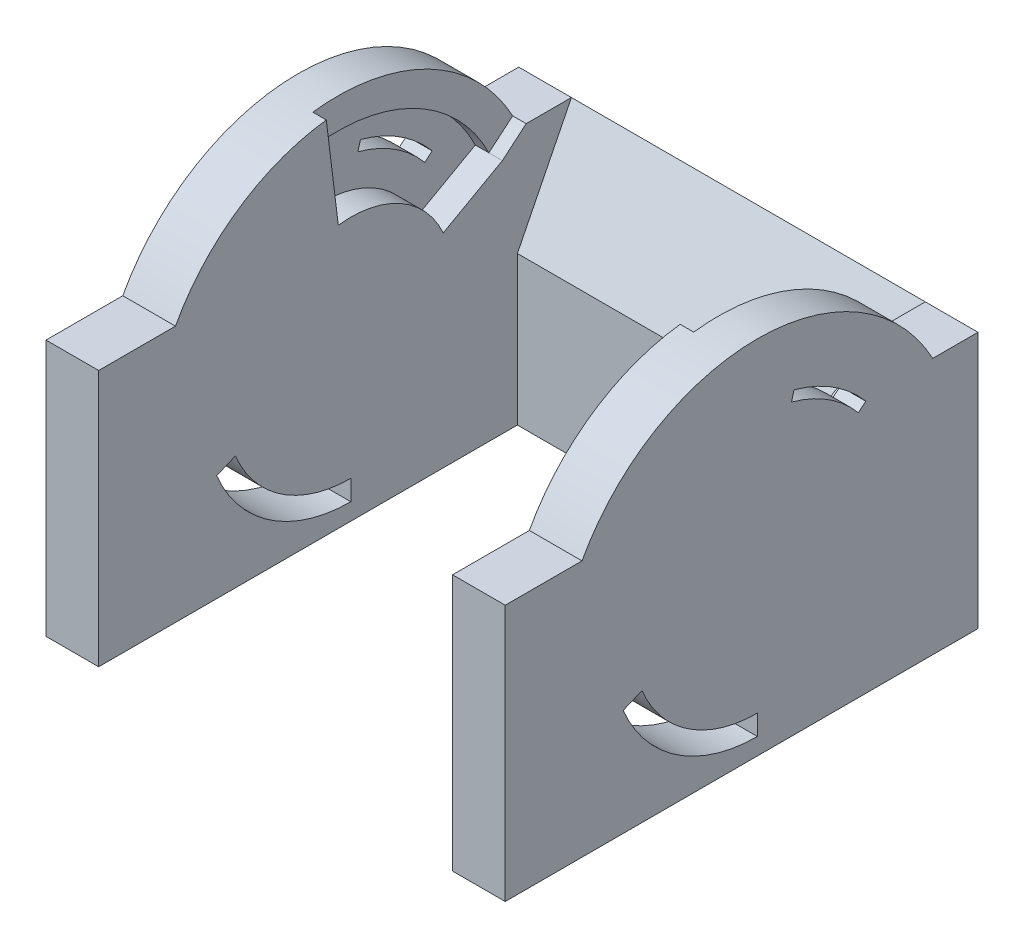
SolidWorks part; units mm, degrees
ref_plane "Alzado" through (0, 0, 0) normal (0, 0, 1) x (1, 0, 0)
ref_plane "Planta" through (0, 0, 0) normal (0, 1, 0) x (1, 0, 0)
ref_plane "Vista lateral" through (0, 0, 0) normal (1, 0, 0) x (0, 0, -1)
sketch "Croquis1" plane through (0, 0, 0) normal (0, 0, 1) x (1, 0, 0)
  line L1 (-48.8873, 14.6225) -> (-14.8873, 14.6225)
  line L2 (-48.8873, 14.6225) -> (-48.8873, -4.3775)
  line L3 (-48.8873, -4.3775) -> (-14.8873, -4.3775)
  line L4 (-14.8873, 14.6225) -> (-14.8873, -4.3775)
  dimension "D1" = 19
  dimension "D2" = 34
extrude "Saliente-Extruir1" add sketch "Croquis1" along normal blind 35
sketch "Croquis2" plane through (0, -4.3775, 0) normal (0, -1, 0) x (1, 0, 0)
  line L0 (-48.8873, 35) -> (-14.8873, 35) construction
  line L1 (-44.9873, 35) -> (-18.7873, 35)
  line L2 (-44.9873, 35) -> (-44.9873, 4)
  line L3 (-44.9873, 4) -> (-18.7873, 4)
  line L4 (-18.7873, 35) -> (-18.7873, 4)
  line L5 (-48.8873, 35) -> (-48.8873, 0) construction
  line L6 (-14.8873, 35) -> (-14.8873, 0) construction
  line L7 (-48.8873, 0) -> (-14.8873, 0) construction
  dimension "D1" = 3.9
  dimension "D2" = 3.9
  dimension "D3" = 26.2
  dimension "D4" = 4
extrude "Cortar-Extruir1" cut sketch "Croquis2" against normal blind 25
sketch "Croquis4" plane through (-18.7873, 0, 0) normal (-1, 0, 0) x (0, 0, 1)
  line L0 (4, 14.6225) -> (4, 6.6225)
  line L1 (4, 14.6225) -> (4, -4.3775) construction
  line L2 (4, 6.6225) -> (0, 14.6225)
  line L3 (0, 14.6225) -> (4, 14.6225)
extrude "Cortar-Extruir3" cut sketch "Croquis4" along normal up to vertex (26.2 mm away) up to point (-44.9873, 14.6225, 4)
sketch "Croquis9" plane through (-14.8873, 0, 0) normal (1, 0, 0) x (0, 0, -1)
  line L0 (-35, 14.6225) -> (0, 14.6225) construction
  line L1 (-29.3158, 14.6225) -> (-3.3495, 14.6225)
  line L7 (-35, -4.3775) -> (0, -4.3775) construction
  arc A0 (-29.3158, 14.6225) -> (-3.3495, 14.6225) centre (-16.3327, 7.6225) cw
  dimension "D2" = 12
extrude "Saliente-Extruir2" add sketch "Croquis9" against normal up to vertex (34 mm away) up to point (-48.8873, 14.6225, 35)
sketch "Croquis10" plane through (0, 14.6225, 0) normal (0, -1, 0) x (1, 0, 0)
  line L1 (-44.9873, 29.3158) -> (-18.7873, 29.3158)
  line L2 (-44.9873, 29.3158) -> (-44.9873, 3.3495)
  line L3 (-44.9873, 3.3495) -> (-18.7873, 3.3495)
  line L4 (-18.7873, 29.3158) -> (-18.7873, 3.3495)
extrude "Cortar-Extruir4" cut sketch "Croquis10" against normal blind 10
sketch "Croquis11" plane through (-14.8873, 0, 0) normal (1, 0, 0) x (0, 0, -1)
  line L0 (-26.2646, 3.5092) -> (-24.8787, 4.0831)
  line L1 (-16.3327, -1.6275) -> (-16.3327, -3.1275)
  line L3 (-13.6215, 17.7406) -> (-13.8072, 17.0476)
  line L4 (-8.3084, 14.3557) -> (-8.858, 13.8945)
  arc A2 (-8.3084, 14.3557) -> (-13.6215, 17.7406) centre (-16.3327, 7.6225) ccw
  arc A3 (-24.8787, 4.0831) -> (-16.3327, -1.6275) centre (-16.3327, 7.6225) ccw
  arc A4 (-13.8072, 17.0476) -> (-8.858, 13.8945) centre (-16.3327, 7.6225) cw
  arc A5 (-26.2646, 3.5092) -> (-16.3327, -3.1275) centre (-16.3327, 7.6225) ccw
extrude "Cortar-Extruir5" cut sketch "Croquis11" against normal up to vertex (34 mm away) up to point (-48.8873, 14.6225, 3.3495)
sketch "Croquis12" plane through (-18.7873, 0, 0) normal (-1, 0, 0) x (0, 0, 1)
  line L0 (17.2589, 15.0651) -> (17.8732, 20.0273)
  line L1 (5.1129, 13.1331) -> (9.4881, 10.6887)
  arc A2 (9.4881, 10.6887) -> (17.2589, 15.0651) centre (16.3327, 7.6225) cw
  arc A3 (5.1129, 13.1331) -> (17.8732, 20.0273) centre (16.3327, 7.6225) cw
extrude "Cortar-Extruir6" cut sketch "Croquis12" against normal blind 2
sketch "Croquis14" plane through (-18.7873, 0, 0) normal (-1, 0, 0) x (0, 0, 1)
  line L0 (5.1129, 13.1331) -> (9.4881, 10.6887) construction
  line L1 (17.8732, 20.0273) -> (17.2589, 15.0651)
  line L2 (9.4881, 10.6887) -> (5.1129, 13.1331)
  arc A0 (17.2589, 15.0651) -> (9.4881, 10.6887) centre (16.3327, 7.6225) ccw
  arc A1 (17.2589, 15.0651) -> (9.4881, 10.6887) centre (16.3327, 7.6225) ccw construction
  arc A2 (17.8732, 20.0273) -> (5.1129, 13.1331) centre (16.3327, 7.6225) ccw
extrude "Cortar-Extruir7" cut sketch "Croquis14" along normal blind 28.2
sketch "Croquis15" plane through (-18.7873, 0, 0) normal (-1, 0, 0) x (0, 0, 1)
  line L0 (17.8732, 20.0273) -> (18.1505, 22.2601)
  line L1 (3.3495, 14.6225) -> (5.1129, 13.1331)
  arc A0 (17.8732, 20.0273) -> (5.1129, 13.1331) centre (16.3327, 7.6225) ccw
  arc A1 (17.8732, 20.0273) -> (5.1129, 13.1331) centre (16.3327, 7.6225) ccw construction
  arc A2 (29.3158, 14.6225) -> (3.3495, 14.6225) centre (16.3327, 7.6225) ccw construction
  arc A3 (18.1505, 22.2601) -> (3.3495, 14.6225) centre (16.3327, 7.6225) ccw
extrude "Cortar-Extruir8" cut sketch "Croquis15" against normal blind 1
extrude "Cortar-Extruir9" cut sketch "Croquis15<2>" along normal blind 27.2
sketch "Croquis15<2>" plane through (-18.7873, 0, 0) normal (-1, 0, 0) x (0, 0, 1) same geometry as "Croquis15"
